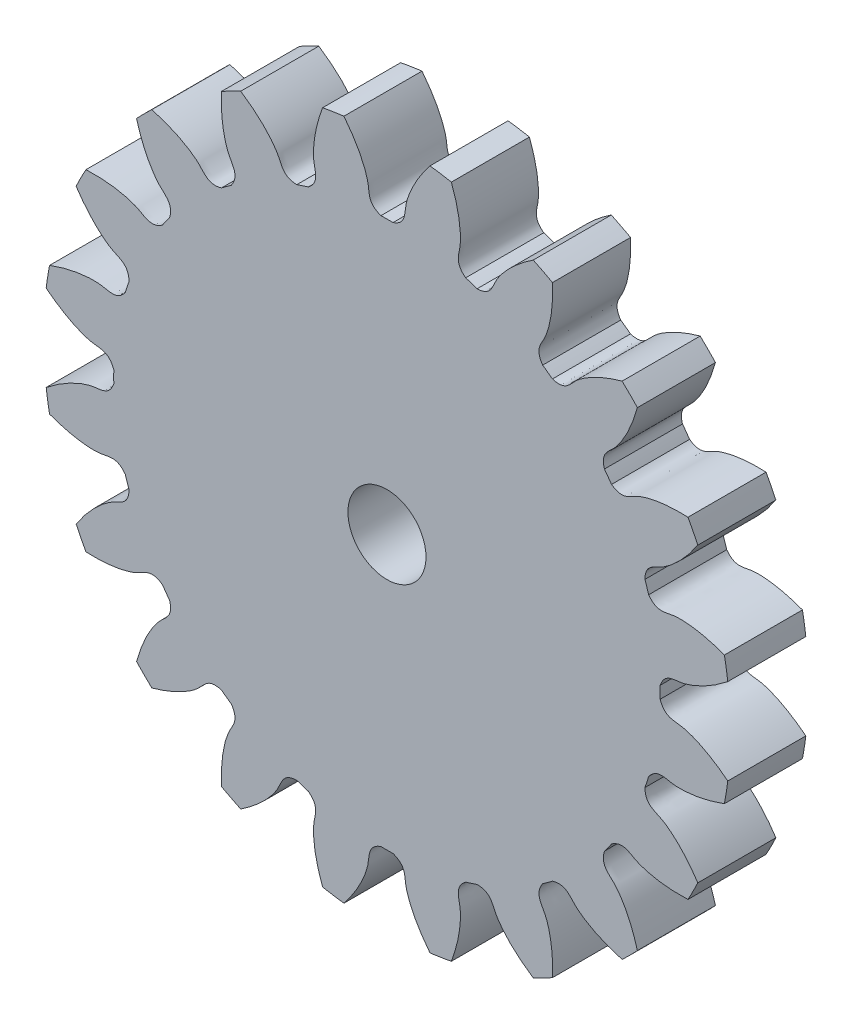
SolidWorks part; units mm, degrees
material "合金钢"
ref_plane "前视基准面" through (0, 0, 0) normal (0, 0, 1) x (1, 0, 0)
ref_plane "上视基准面" through (0, 0, 0) normal (0, 1, 0) x (1, 0, 0)
ref_plane "右视基准面" through (0, 0, 0) normal (1, 0, 0) x (0, 0, -1)
sketch "草图1" plane through (0, 0, 0) normal (0, 0, 1) x (1, 0, 0)
  circle A0 centre (0, 0) radius 44
extrude "凸台-拉伸1" add sketch "草图1" along normal blind 10
ref_axis "基准轴1" through (0, 0, -1.5) along (0, 0, 1)
sketch "草图2" plane through (0, 0, 0) normal (0, 0, 1) x (1, 0, 0)
  line L0 (0, 0) -> (0, 44) construction
  circle A0 centre (0, 0) radius 44 construction
  arc A1 (0.7733, 34.9915) -> (-0.7733, 34.9915) centre (0, 0) ccw
  arc A2 (12.7246, 49.993) -> (-12.7246, 49.993) centre (0, 0) ccw
  spline S0 degree 3 poles (0.7733, 34.9915) (2.4448, 35.5739) (2.2283, 36.7485) (2.4516, 37.88) (2.4756, 37.9902) (2.5052, 38.1145) (2.5412, 38.2528) (2.5839, 38.4048) (2.634, 38.5703) (2.6921, 38.749) (2.7587, 38.9408) (2.8343, 39.1453) (2.9194, 39.3622) (3.0147, 39.5913) (3.1205, 39.8322) (3.2375, 40.0846) (3.3661, 40.3481) (3.5067, 40.6223) (3.66, 40.9069) (3.8263, 41.2015) (4.0061, 41.5057) (4.1999, 41.819) (4.4081, 42.141) (4.6311, 42.4712) (4.8692, 42.8092) (5.1231, 43.1545) (5.3929, 43.5065) (5.679, 43.8649) (5.9819, 44.229) (6.3019, 44.5983) (6.6392, 44.9724) (6.9943, 45.3506) (7.3673, 45.7323) (7.7587, 46.1171) (8.1686, 46.5043) (8.5972, 46.8933) (9.0449, 47.2836) (9.5119, 47.6745) (9.9983, 48.0653) (10.5043, 48.4556) (11.0301, 48.8446) (11.7659, 49.3666) (12.3357, 49.7453) (12.7246, 49.993) knots 0 0 0 0 0.165916 0.170906 0.176664 0.183189 0.190482 0.198542 0.207371 0.216967 0.22733 0.238462 0.250361 0.263027 0.276462 0.290664 0.305634 0.321371 0.337876 0.355149 0.37319 0.391998 0.411574 0.431917 0.453028 0.474907 0.497554 0.520968 0.54515 0.570099 0.595817 0.622302 0.649554 0.677575 0.706363 0.735918 0.766242 0.797333 0.829191 0.861818 0.895212 0.929373 1 1 1 1
  spline S1 degree 3 poles (-0.7733, 34.9915) (-2.4448, 35.5739) (-2.2283, 36.7485) (-2.4516, 37.88) (-2.4756, 37.9902) (-2.5052, 38.1145) (-2.5412, 38.2528) (-2.5839, 38.4048) (-2.634, 38.5703) (-2.6921, 38.749) (-2.7587, 38.9408) (-2.8343, 39.1453) (-2.9194, 39.3622) (-3.0147, 39.5913) (-3.1205, 39.8322) (-3.2375, 40.0846) (-3.3661, 40.3481) (-3.5067, 40.6223) (-3.66, 40.9069) (-3.8263, 41.2015) (-4.0061, 41.5057) (-4.1999, 41.819) (-4.4081, 42.141) (-4.6311, 42.4712) (-4.8692, 42.8092) (-5.1231, 43.1545) (-5.3929, 43.5065) (-5.679, 43.8649) (-5.9819, 44.229) (-6.3019, 44.5983) (-6.6392, 44.9724) (-6.9943, 45.3506) (-7.3673, 45.7323) (-7.7587, 46.1171) (-8.1686, 46.5043) (-8.5972, 46.8933) (-9.0449, 47.2836) (-9.5119, 47.6745) (-9.9983, 48.0653) (-10.5043, 48.4556) (-11.0301, 48.8446) (-11.7659, 49.3666) (-12.3357, 49.7453) (-12.7246, 49.993) knots 0 0 0 0 0.165916 0.170906 0.176664 0.183189 0.190482 0.198542 0.207371 0.216967 0.22733 0.238462 0.250361 0.263027 0.276462 0.290664 0.305634 0.321371 0.337876 0.355149 0.37319 0.391998 0.411574 0.431917 0.453028 0.474907 0.497554 0.520968 0.54515 0.570099 0.595817 0.622302 0.649554 0.677575 0.706363 0.735918 0.766242 0.797333 0.829191 0.861818 0.895212 0.929373 1 1 1 1
extrude "切除-拉伸1" cut sketch "草图2" along normal through all
pattern_circular "阵列(圆周)1" count 20 every 18 about axis through (0, 0, -1.5) along (0, 0, 1) of "切除-拉伸1"
sketch "草图3" plane through (0, 0, 0) normal (0, 0, 1) x (1, 0, 0)
  circle A0 centre (0, 0) radius 40 construction
  dimension "Dn" = 80
sketch "草图4" plane through (0, 0, 10) normal (0, 0, 1) x (1, 0, 0)
  circle A0 centre (0, 0) radius 5
  dimension "D1" = 10
extrude "切除-拉伸2" cut sketch "草图4" against normal blind 10
